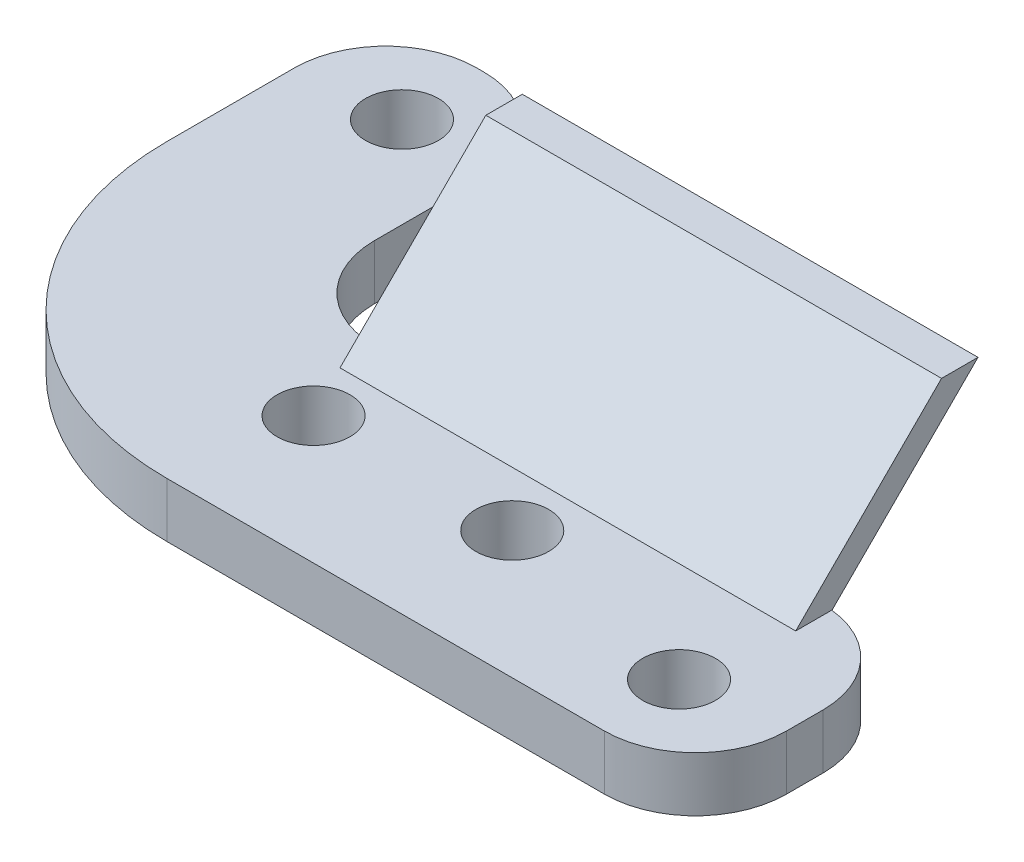
SolidWorks part; units mm, degrees
material "ABS PC"
ref_plane "Front Plane" through (0, 0, 0) normal (0, 0, 1) x (1, 0, 0)
ref_plane "Top Plane" through (0, 0, 0) normal (0, 1, 0) x (1, 0, 0)
ref_plane "Right Plane" through (0, 0, 0) normal (1, 0, 0) x (0, 0, -1)
sketch "Sketch1" plane through (0, 0, 0) normal (0, 1, 0) x (1, 0, 0)
  line L1 (22.5, -14) -> (-22.5, -14)
  line L2 (22.5, -14) -> (22.5, 14)
  line L3 (22.5, 14) -> (-22.5, 14)
  line L4 (-22.5, -14) -> (-22.5, 14)
  line L5 (22.5, -14) -> (-22.5, 14) construction
  line L6 (22.5, 14) -> (-22.5, -14) construction
  point P0 (0, 0)
  dimension "D1" = 28
  dimension "D2" = 45
extrude "Boss-Extrude1" add sketch "Sketch1" along normal blind 3
hole_wizard "Ø4.0 (4) Diameter Hole1" positions "Sketch2" profile "Sketch3" hole size "Ø4.0" standard "ANSI Metric" end condition through all
sketch "Sketch2" plane through (0, 3, 0) normal (0, 1, 0) x (1, 0, 0)
  line L1 (17.1, -9.5) -> (-17.1, -9.5)
  line L2 (17.1, -9.5) -> (17.1, 9.5)
  line L3 (17.1, 9.5) -> (-17.1, 9.5)
  line L4 (-17.1, -9.5) -> (-17.1, 9.5)
  line L5 (17.1, -9.5) -> (-17.1, 9.5) construction
  line L6 (17.1, 9.5) -> (-17.1, -9.5) construction
  line L7 (0, 14) -> (0, 0) construction
  line L8 (22.5, 14) -> (-22.5, 14) construction
  line L9 (0, 0) -> (0, -14) construction
  line L10 (-22.5, -14) -> (22.5, -14) construction
  point P2 (-17.1, 9.5)
  point P5 (17.1, -9.5)
  dimension "D1" = 19
  dimension "D2" = 34.2
sketch "Sketch3" plane through (-17.1, 3, -9.5) normal (1, 0, 0) x (0, 0, 1)
  line L0 (0, 0) -> (0, 3)
  line L1 (0, 3) -> (2, 3)
  line L2 (2, 3) -> (2, 0)
  line L5 (2, 0) -> (0, 0)
  line L11 (0, -6.35) -> (0, 107.95) construction
  dimension "Thru Hole Dia." = 4
  dimension "Thru Hole Depth" = 3
sketch "Sketch4" plane through (0, 3, 0) normal (0, 1, 0) x (1, 0, 0)
  line L0 (-22.5, -14) -> (22.5, -14) construction
  line L1 (9, -9) -> (-9, -9)
  line L2 (9, -9) -> (9, -14)
  line L3 (9, -14) -> (-9, -14)
  line L4 (-9, -9) -> (-9, -14)
  line L5 (9, -9) -> (-9, -14) construction
  line L6 (9, -14) -> (-9, -9) construction
  line L7 (0, -11.5) -> (0, 0) construction
  point P0 (0, -11.5)
  dimension "D1" = 18
  dimension "D2" = 5
extrude "Cut-Extrude1" [suppressed] cut sketch "Sketch4" against normal blind 3
hole_wizard "Ø4.0 (4) Diameter Hole2" positions "Sketch7" profile "Sketch8" hole size "Ø4.0" standard "ANSI Metric" end condition through all
sketch "Sketch7" plane through (0, 3, 0) normal (0, 1, 0) x (1, 0, 0)
  line L0 (0, 18.0075) -> (0, 15.2248) construction
  line L2 (-22.5, -14) -> (22.5, -14) construction
  point P0 (-5.45, -7)
  point P7 (5.45, -7)
  dimension "D1" = 10.9
  dimension "D2" = 7
sketch "Sketch8" plane through (-5.45, 3, 7) normal (1, 0, 0) x (0, 0, 1)
  line L0 (0, 0) -> (0, 3)
  line L1 (0, 3) -> (2, 3)
  line L2 (2, 3) -> (2, 0)
  line L5 (2, 0) -> (0, 0)
  line L11 (0, -6.35) -> (0, 107.95) construction
  dimension "Thru Hole Dia." = 4
  dimension "Thru Hole Depth" = 3
sketch "Sketch10" plane through (0, 3, 0) normal (0, 1, 0) x (1, 0, 0)
  line L0 (-12.1, 14) -> (-12.1, -2)
  line L1 (22.5, 14) -> (-22.5, 14) construction
  line L2 (-12.1, -2) -> (22.5, -2)
  line L3 (22.5, -14) -> (22.5, 14) construction
  line L4 (22.5, -2) -> (22.5, 14)
  line L5 (22.5, 14) -> (-12.1, 14)
  line L6 (-22.5, -14) -> (22.5, -14) construction
  circle A0 centre (-17.1, 9.5) radius 2 construction
  dimension "D1" = 5
  dimension "D2" = 12
extrude "Cut-Extrude2" cut sketch "Sketch10" against normal blind 3
fillet "Fillet2" radius 5 5 edges at (22.5, 1.5, 2) (22.5, 1.5, 14) (-22.5, 1.5, -14) (-12.1, 1.5, -14) (-12.1, 1.5, 2)
fillet "Fillet3" radius 16 1 edges at (-22.5, 1.5, 14)
ref_plane "Plane1" through (23, 0, 0) normal (1, 0, 0) x (0, 0, -1)
sketch "Sketch11" plane through (23, 0, 0) normal (1, 0, 0) x (0, 0, -1)
  line L0 (-4, 3) -> (4, 11)
  line L1 (4, 11) -> (6, 11)
  line L2 (6, 11) -> (-2, 3)
  line L3 (3, 3) -> (-2, 3) construction
  line L4 (-2, 3) -> (-4, 3)
  line L5 (-2, 3) -> (0.978, 3) construction
  line L6 (-2, 0) -> (-2, 3) construction
  point P3 (-5.7227, 3)
  point P9 (-4, 3)
  dimension "D1" = 45
  dimension "D2" = 2
  dimension "D3" = 8
extrude "Boss-Extrude2" add sketch "Sketch11" against normal blind 25 from offset 5 offset against normal yes
sketch "Sketch12" plane through (0, 0, 0) normal (0, -1, 0) x (1, 0, 0)
  line L0 (-2.9034, 2) -> (-2.9034, 3.5)
  line L1 (-7, 2) -> (17.5, 2) construction
  line L2 (-2.9034, 3.5) -> (14.5171, 3.5)
  line L3 (14.5171, 3.5) -> (14.5171, 2)
  line L4 (-2.9034, 2) -> (14.5171, 2)
  dimension "D1" = 1.5
extrude "Cut-Extrude3" cut sketch "Sketch12" against normal blind 3
fillet "Fillet4" radius 2 2 edges at (-2.9034, 1.5, 2) (14.5171, 1.5, 2)
chamfer "Chamfer1" distance 2 angle 45 2 edges at (-3.6152, 3, 2.4189) (15.2289, 3, 2.4189)
